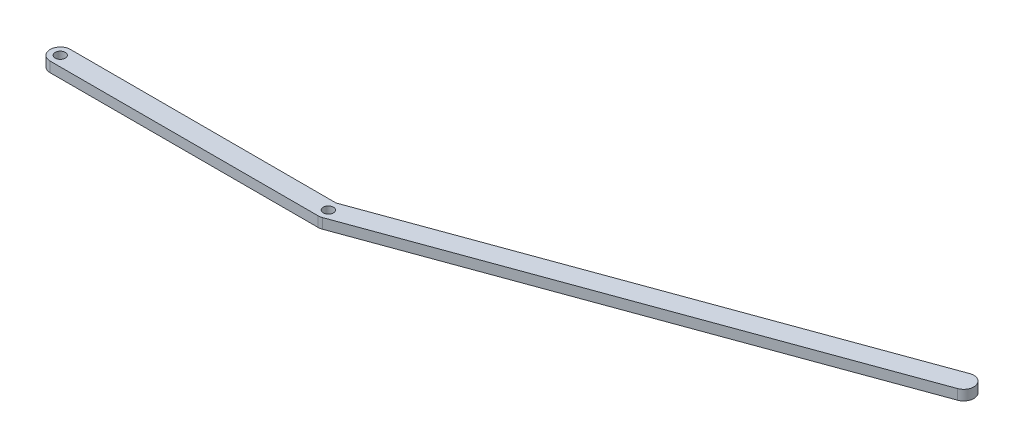
SolidWorks part; units mm, degrees
ref_plane "Front Plane" through (0, 0, 0) normal (0, 0, 1) x (1, 0, 0)
ref_plane "Top Plane" through (0, 0, 0) normal (0, 1, 0) x (1, 0, 0)
ref_plane "Right Plane" through (0, 0, 0) normal (1, 0, 0) x (0, 0, -1)
sketch "Sketch1" plane through (0, 0, 0) normal (0, 1, 0) x (1, 0, 0)
  line L0 (0, 0) -> (-265, 0) construction
  line L1 (0, 0) -> (460.4494, 167.5899) construction
  line L2 (-3.4202, 9.3969) -> (457.0292, 176.9868) construction
  line L3 (-3.4202, 9.3969) -> (3.4202, -9.3969) construction
  line L4 (457.0292, 176.9868) -> (463.8696, 158.1929) construction
  line L5 (3.4202, -9.3969) -> (463.8696, 158.1929) construction
  line L6 (-3.4202, 9.3969) -> (463.8696, 158.1929) construction
  line L7 (457.0292, 176.9868) -> (3.4202, -9.3969) construction
  line L8 (0, -10) -> (-265, -10) construction
  line L9 (0, -10) -> (0, 10) construction
  line L10 (-265, -10) -> (-265, 10) construction
  line L11 (0, 10) -> (-265, 10) construction
  line L12 (0, -10) -> (-265, 10) construction
  line L13 (-265, -10) -> (0, 10) construction
  line L14 (-265, 10) -> (-2.2245, 9.8321)
  line L15 (-2.2245, 9.8321) -> (457.0292, 176.9868)
  line L16 (463.8696, 158.1929) -> (3.4202, -9.3969)
  line L17 (0, -10) -> (-265, -10)
  arc A0 (-265, -10) -> (-265, 10) centre (-265, 0) cw
  arc A1 (457.0292, 176.9868) -> (463.8696, 158.1929) centre (460.4494, 167.5899) cw
  arc A2 (3.4202, -9.3969) -> (0, -10) centre (0, 0) cw
  circle A3 centre (-265, 0) radius 5
  circle A4 centre (0, 0) radius 5
  circle A5 centre (460.4494, 167.5899) radius 5
  point P5 (230.2247, 83.7949)
  point P6 (-132.5, 0)
  dimension "D5" = 10
  dimension "D6" = 10
  dimension "D7" = 10
  dimension "D1" = 265
  dimension "D2" = 490
  dimension "D3" = 20
  dimension "D4" = 20
extrude "Boss-Extrude1" add sketch "Sketch1" along normal mid plane 10 contours A2 L16 A1 L15 L14 A0 L17 A5 A4 A3 region at (-133.6172, 0, -2.2292)
sketch "Sketch2" plane through (0, 0, 0) normal (0, 1, 0) x (1, 0, 0)
  circle A0 centre (460.4494, 167.5899) radius 5
extrude "Boss-Extrude2" add sketch "Sketch2" along normal mid plane 10
